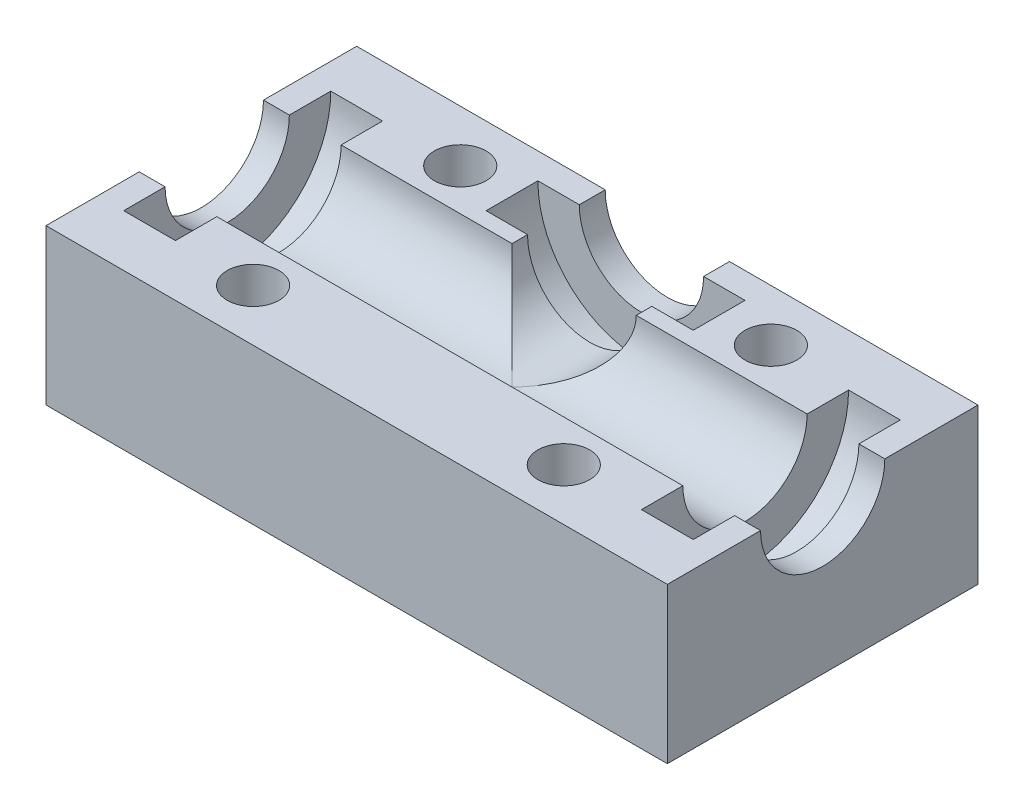
SolidWorks part; units mm, degrees
ref_plane "Front Plane" through (0, 0, 0) normal (0, 0, 1) x (1, 0, 0)
ref_plane "Top Plane" through (0, 0, 0) normal (0, 1, 0) x (1, 0, 0)
ref_plane "Right Plane" through (0, 0, 0) normal (1, 0, 0) x (0, 0, -1)
sketch "Sketch1" plane through (0, 0, 0) normal (0, 1, 0) x (1, 0, 0)
  line L0 (0, 15) -> (60, 15) construction
  line L1 (0, 30) -> (60, 30)
  line L2 (0, 30) -> (0, 0)
  line L3 (0, 0) -> (60, 0)
  line L4 (60, 30) -> (60, 0)
  line L5 (30, 30) -> (30, 0) construction
  line L6 (45, 25) -> (60, 25) construction
  line L7 (45, 25) -> (45, 30) construction
  circle A0 centre (45, 25) radius 2.5
  circle A1 centre (45, 5) radius 2.5
  circle A2 centre (15, 5) radius 2.5
  circle A3 centre (15, 25) radius 2.5
  dimension "D3" = 5
  dimension "D1" = 60
  dimension "D2" = 30
  dimension "D4" = 15
  dimension "D5" = 5
extrude "Boss-Extrude1" add sketch "Sketch1" along normal blind 30
sketch "Sketch2" plane through (0, 0, 0) normal (-1, 0, 0) x (0, 0, 1)
  line L0 (-15, 30) -> (-15, 0) construction
  line L1 (-30, 30) -> (0, 30) construction
  line L2 (-30, 0) -> (0, 0) construction
  line L3 (-30, 15) -> (0, 15) construction
  line L4 (-30, 30) -> (-30, 0) construction
  line L5 (0, 30) -> (0, 0) construction
  circle A0 centre (-15, 15) radius 6
  circle A1 centre (-15, 15) radius 10
  dimension "D1" = 12
  dimension "D2" = 20
extrude "Cut-Extrude1" cut sketch "Sketch2" against normal through all contours A0
extrude "Cut-Extrude2" cut sketch "Sketch2<4>" against normal blind 5 from offset 2.5 offset against normal yes
sketch "Sketch2<4>" plane through (0, 0, 0) normal (-1, 0, 0) x (0, 0, 1) same geometry as "Sketch2"
ref_plane "Plane1" through (30, 0, 0) normal (-1, 0, 0) x (0, 0, 1)
mirror "Mirror1" about plane through (30, 0, 0) normal (-1, 0, 0) of "Cut-Extrude2"
sketch "Sketch6" plane through (0, 0, -30) normal (0, 0, -1) x (-1, 0, 0)
  line L0 (-60, 30) -> (0, 0) construction
  line L1 (-60, 0) -> (0, 30) construction
  circle A0 centre (-30, 15) radius 6
  circle A1 centre (-30, 15) radius 10
  dimension "D1" = 12
  dimension "D2" = 20
extrude "Cut-Extrude5" cut sketch "Sketch6" against normal blind 15 contours A0
ref_plane "Plane2" through (0, 15, 0) normal (0, -1, 0) x (-1, 0, 0)
extrude "Cut-Extrude6" cut sketch "Sketch6<3>" against normal blind 5 from offset 2.5 contours A0 | A1 A0 region at (30, 15, -30) region at (39.7172, 15, -30) offset against normal yes
sketch "Sketch6<3>" plane through (0, 0, -30) normal (0, 0, -1) x (-1, 0, 0) same geometry as "Sketch6"
split "Split2" trim tools "Plane2" bodies to split 109 resulting bodies 112 113
delete or keep bodies "Body-Delete/Keep 1" type delete bodies bodies 112
equation "\"WIDTH_CENTRE\"= 0.06m"
equation "\"LENGTH_CENTRE\"= 0.03m"
equation "\"D1@Sketch1\"=\"WIDTH_CENTRE\""
equation "\"D2@Sketch1\"=\"LENGTH_CENTRE\""
equation "\"HEIGHT_CENTRE\"=0.03"
equation "\"D1@Boss-Extrude1\"=\"HEIGHT_CENTRE\""
equation "\"SIDE_SHAFT_DIAM\"= 12mm"
equation "\"D1@Sketch2\"=\"SIDE_SHAFT_DIAM\""
equation "\"OUTER_DIAM_SIDE_BEARINGS\"= 0.02"
equation "\"D2@Sketch2\"=\"OUTER_DIAM_SIDE_BEARINGS\""
equation "\"SIDE_BEARING_WIDTH\" = 0.005"
equation "\"D1@Cut-Extrude2\"= \"SIDE_BEARING_WIDTH\""
equation "\"SIDE_INSERT_EDGE\"=0.003"
equation "\"SIDE_INSERT_DIAM\"= 0.003"
equation "\"SIDE_INSERT_DEPTH\"=0.01"
equation "\"CENTRE_SHAFT_DIAM\" = 12mm"
equation "\"D1@Sketch6\"= \"CENTRE_SHAFT_DIAM\""
equation "\"OUTER_DIAM_CENTRE_BEARINGS\"= 0.02m"
equation "\"D2@Sketch6\"=\"OUTER_DIAM_CENTRE_BEARINGS\""
equation "\"D1@Cut-Extrude5\"=\"LENGTH_CENTRE\"*0.5"
equation "\"SIDE_BEARING_LIP_DEPTH\"= 0.0025"
equation "\"D19@Cut-Extrude2\"=\"SIDE_BEARING_LIP_DEPTH\""
equation "\"CENTRE_BEARING_LIP_DEPTH\" = 0.0025"
equation "\"D19@Cut-Extrude6\"=\"CENTRE_BEARING_LIP_DEPTH\""
equation "\"CENTRE_BEARING_WIDTH\"= 0.005"
equation "\"D1@Cut-Extrude6\"=\"CENTRE_BEARING_WIDTH\""
equation "\"FASTENER_HOLE_OFFSET_X\" = 0.015"
equation "\"D4@Sketch1\"=\"FASTENER_HOLE_OFFSET_X\""
equation "\"FASTENER_DIAM\" = 0.005"
equation "\"D3@Sketch1\"=\"FASTENER_DIAM\""
equation "\"FASTENER_HOLE_OFFSET_Z\" = 0.005"
equation "\"D5@Sketch1\"=\"FASTENER_HOLE_OFFSET_Z\""
